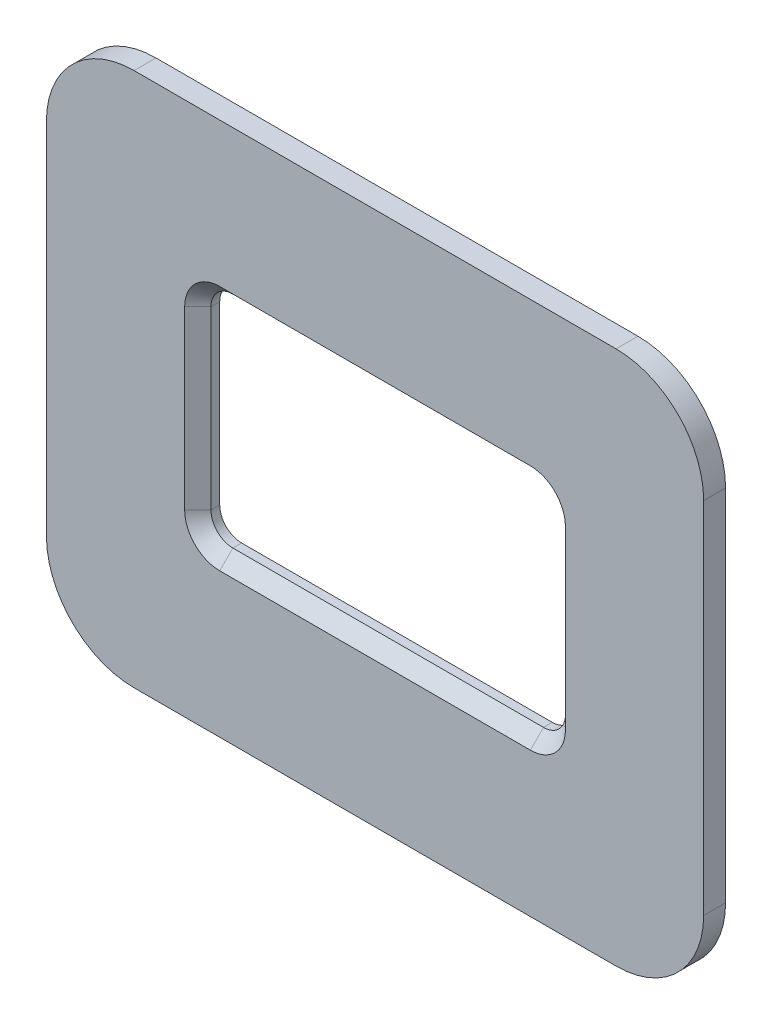
SolidWorks part; units mm, degrees
ref_plane "前视基准面" through (0, 0, 0) normal (0, 0, 1) x (1, 0, 0)
ref_plane "上视基准面" through (0, 0, 0) normal (0, 1, 0) x (1, 0, 0)
ref_plane "右视基准面" through (0, 0, 0) normal (1, 0, 0) x (0, 0, -1)
other "Configuration Table"
sketch "草图1" plane through (0, 0, 0) normal (0, 0, 1) x (1, 0, 0)
  line L1 (-55, -61) -> (55, -61)
  line L2 (-75, -41) -> (-75, 41)
  line L3 (-55, 61) -> (55, 61)
  line L4 (75, -41) -> (75, 41)
  line L5 (-75, -61) -> (75, 61) construction
  line L6 (-75, 61) -> (75, -61) construction
  line L7 (-35.45, -25.1) -> (35.45, -25.1)
  line L8 (-40.45, -20.1) -> (-40.45, 20.1)
  line L9 (-35.45, 25.1) -> (35.45, 25.1)
  line L10 (40.45, -20.1) -> (40.45, 20.1)
  line L11 (-40.45, -25.1) -> (40.45, 25.1) construction
  line L12 (-40.45, 25.1) -> (40.45, -25.1) construction
  arc A0 (55, 61) -> (75, 41) centre (55, 41) cw
  arc A1 (55, -61) -> (75, -41) centre (55, -41) ccw
  arc A2 (-55, -61) -> (-75, -41) centre (-55, -41) cw
  arc A3 (-75, 41) -> (-55, 61) centre (-55, 41) cw
  arc A4 (35.45, 25.1) -> (40.45, 20.1) centre (35.45, 20.1) cw
  arc A5 (35.45, -25.1) -> (40.45, -20.1) centre (35.45, -20.1) ccw
  arc A6 (-35.45, -25.1) -> (-40.45, -20.1) centre (-35.45, -20.1) cw
  arc A7 (-40.45, 20.1) -> (-35.45, 25.1) centre (-35.45, 20.1) cw
  point P0 (0, 0)
  point P18 (0, 0)
  dimension "D3" = 20
  dimension "D6" = 5
  dimension "D1" = 150
  dimension "D2" = 122
  dimension "D4" = 80.9
  dimension "D5" = 50.2
extrude "凸台-拉伸1" add sketch "草图1" along normal blind 5
chamfer "倒角1" distance 3 8 edges at (0, -25.1, 5) (38.9855, -23.6355, 5) (-38.9855, -23.6355, 5) (40.45, 0, 5) (-40.45, 0, 5) (38.9855, 23.6355, 5) (-38.9855, 23.6355, 5) (0, 25.1, 5)
